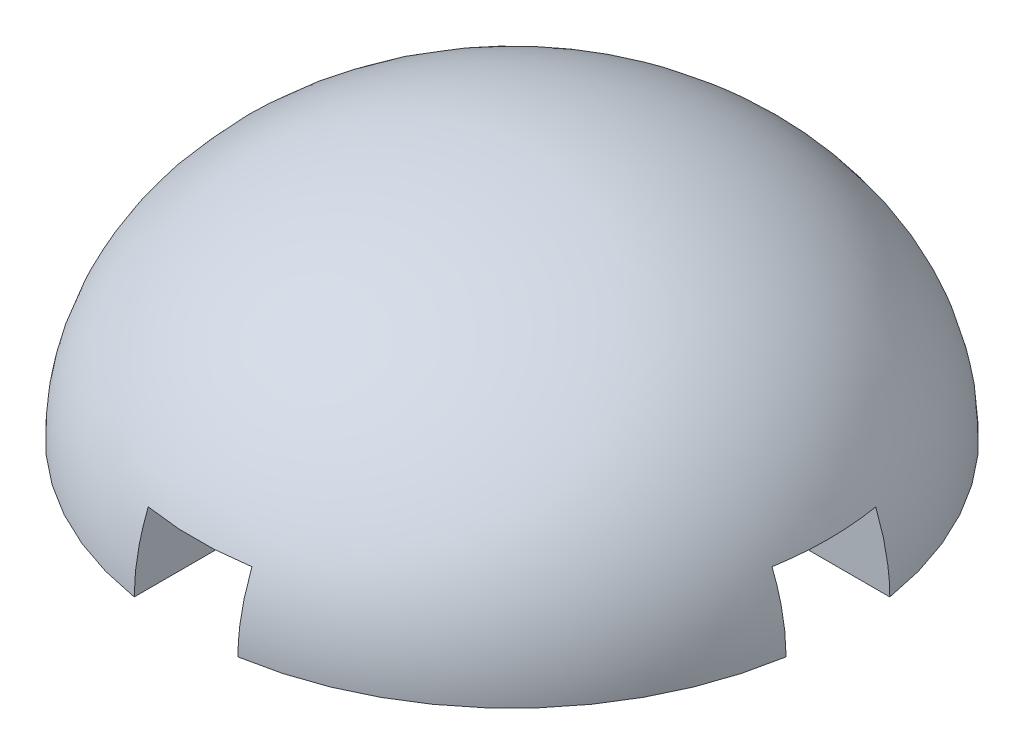
SolidWorks part; units mm, degrees
ref_plane "Front Plane" through (0, 0, 0) normal (0, 0, 1) x (1, 0, 0)
ref_plane "Top Plane" through (0, 0, 0) normal (0, 1, 0) x (1, 0, 0)
ref_plane "Right Plane" through (0, 0, 0) normal (1, 0, 0) x (0, 0, -1)
sketch "Sketch2" plane through (0, 0, 0) normal (0, 0, 1) x (1, 0, 0)
  line L0 (0, 0) -> (0, 17.5)
  line L2 (17.5, 0) -> (0, 0)
  arc A0 (17.5, 0) -> (0, 17.5) centre (0, 0) ccw
  dimension "D1" = 35
revolve "Revolve1" add sketch "Sketch2" angle 360 about L0
scale "Scale1" scale about centroid uniform scaling no x scale factor 1 y scale factor 0.75 z scale factor 1
ref_axis "Axis1" through (0, 0.9844, 0) along (0, 1, 0)
sketch "Sketch3" plane through (0, 0, 0) normal (0, 0, 1) x (1, 0, 0)
  line L3 (-2.75, 5.4063) -> (-2.75, 1.6406)
  line L9 (-2.75, 5.4063) -> (2.75, 5.4063)
  line L18 (-17.5, 1.6406) -> (17.5, 1.6406) construction
  line L19 (2.75, 1.6406) -> (2.75, 5.4063)
  line L20 (2.75, 1.6406) -> (-2.75, 1.6406)
  point P5 (-3.3894, 1.4063)
  point P9 (0.2443, 1.4063)
  point P11 (0, 5.4063)
  point P12 (0.2443, 1.4063)
  point P14 (0, 5.4063)
  dimension "D1" = 5.5
extrude "Cut-Extrude1" cut sketch "Sketch3" along normal mid plane 35
pattern_circular "CirPattern1" count 2 every 90 about axis through (0, 0.9844, 0) along (0, 1, 0) of "Cut-Extrude1"
sketch "Sketch4" plane through (0, 5.4063, 0) normal (0, -1, 0) x (1, 0, 0)
  circle A0 centre (0, 0) radius 2.5
  circle A1 centre (0, 0) radius 1.05
  dimension "D1" = 5
  dimension "D2" = 2.1
extrude "Boss-Extrude1" add sketch "Sketch4" along normal up to surface (3.7656 mm away) up to face at (8.3802, 1.6406, 8.3802)
sketch "Sketch5" plane through (0, 5.4063, 0) normal (0, -1, 0) x (1, 0, 0)
  circle A0 centre (0, 0) radius 1.05
extrude "Cut-Extrude2" cut sketch "Sketch5" against normal blind 8
